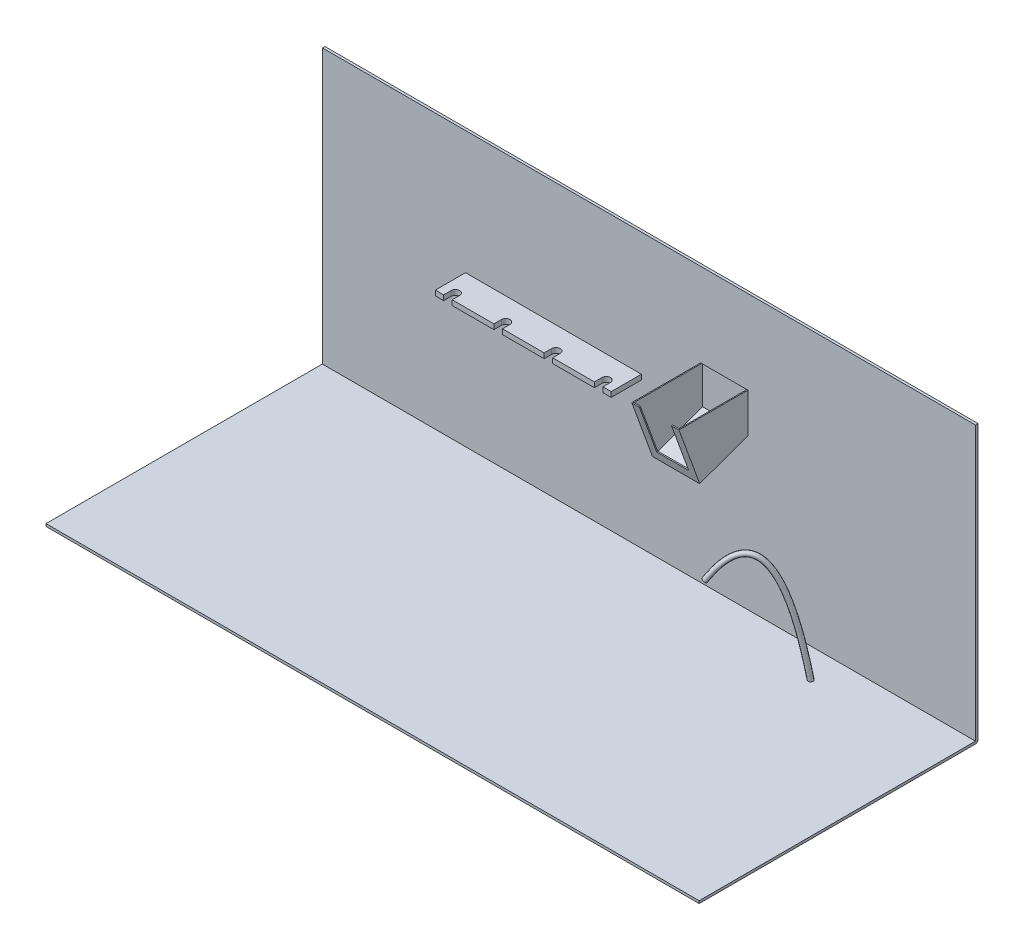
SolidWorks part; units mm, degrees
ref_plane "Front Plane" through (0, 0, 0) normal (0, 0, 1) x (1, 0, 0)
ref_plane "Top Plane" through (0, 0, 0) normal (0, 1, 0) x (1, 0, 0)
ref_plane "Right Plane" through (0, 0, 0) normal (1, 0, 0) x (0, 0, -1)
sketch "Sketch1" plane through (0, 0, 0) normal (0, 0, 1) x (1, 0, 0)
  line L1 (-650, -2.5) -> (650, -2.5)
  line L2 (-650, -2.5) -> (-650, 2.5)
  line L3 (-650, 2.5) -> (650, 2.5)
  line L4 (650, -2.5) -> (650, 2.5)
  line L5 (-650, -2.5) -> (650, 2.5) construction
  line L6 (-650, 2.5) -> (650, -2.5) construction
  point P0 (0, 0)
  dimension "D1" = 5
  dimension "D2" = 1300
extrude "Boss-Extrude1" add sketch "Sketch1" along normal mid plane 550
sketch "Sketch2" plane through (0, 0, -275) normal (0, 0, -1) x (-1, 0, 0)
  line L0 (-650, -2.5) -> (-650, 547.5)
  line L1 (-650, 547.5) -> (650, 547.5)
  line L2 (650, 547.5) -> (650, -2.5)
  line L3 (650, -2.5) -> (-650, -2.5)
  line L4 (650, 2.5) -> (650, -2.5) construction
  dimension "D1" = 550
extrude "Boss-Extrude2" add sketch "Sketch2" along normal blind 5
fillet "Fillet1" radius 5 1 edges at (0, -2.5, -280)
sketch "Sketch3" plane through (0, 0, -275) normal (0, 0, 1) x (1, 0, 0)
  line L0 (-650, 2.5) -> (-650, 547.5) construction
  line L1 (-365, 302.5) -> (-15, 302.5)
  line L2 (-365, 302.5) -> (-365, 292.5)
  line L3 (-365, 292.5) -> (-15, 292.5)
  line L4 (-15, 302.5) -> (-15, 292.5)
  line L5 (-365, 302.5) -> (-15, 292.5) construction
  line L6 (-365, 292.5) -> (-15, 302.5) construction
  line L8 (650, 2.5) -> (-650, 2.5) construction
  point P0 (-190, 297.5)
  dimension "D1" = 350
  dimension "D2" = 460
  dimension "D3" = 10
  dimension "D4" = 300
extrude "Boss-Extrude3" add sketch "Sketch3" along normal blind 60
sketch "Sketch4" plane through (0, 302.5, 0) normal (0, 1, 0) x (1, 0, 0)
  line L0 (-348.5, 230) -> (-348.5, 215)
  line L1 (-15, 215) -> (-365, 215) construction
  line L2 (-331.5, 230) -> (-331.5, 215)
  line L3 (-331.5, 215) -> (-348.5, 215)
  line L4 (-365, 215) -> (-365, 275) construction
  arc A0 (-331.5, 230) -> (-348.5, 230) centre (-340, 230) ccw
  dimension "D1" = 17
  dimension "D3" = 25
  dimension "D2" = 15
extrude "Cut-Extrude1" cut sketch "Sketch4" against normal up to next
pattern_linear "LPattern1" count 4 spacing 100 along (1, 0, 0) of "Cut-Extrude1"
sketch "Sketch5" [suppressed] plane through (0, 0, -275) normal (0, 0, 1) x (1, 0, 0)
  line L0 (160, 597.5) -> (160, 186.1013) construction
  line L1 (-650, 597.5) -> (650, 597.5) construction
  line L2 (650, 597.5) -> (650, 2.5) construction
  line L3 (115, 357.5) -> (205, 357.5)
  line L4 (205, 357.5) -> (205, 467.5)
  line L5 (205, 467.5) -> (210, 467.5)
  line L6 (210, 467.5) -> (210, 352.5)
  line L7 (210, 352.5) -> (110, 352.5)
  line L8 (110, 352.5) -> (110, 467.5)
  line L9 (110, 467.5) -> (115, 467.5)
  line L10 (115, 467.5) -> (115, 357.5)
  line L11 (650, 2.5) -> (-650, 2.5) construction
  dimension "D1" = 490
  dimension "D2" = 90
  dimension "D3" = 5
  dimension "D4" = 5
  dimension "D5" = 5
  dimension "D6" = 110
  dimension "D7" = 350
extrude "Boss-Extrude4" [suppressed] add sketch "Sketch5" along normal blind 100
sketch "Sketch6" [suppressed] plane through (0, 357.5, 0) normal (0, 1, 0) x (1, 0, 0)
  line L0 (115, 231.5) -> (205, 231.5)
  line L1 (115, 175) -> (115, 275) construction
  line L2 (205, 175) -> (205, 275) construction
  line L3 (115, 231.5) -> (115, 235.5)
  line L4 (205, 218.5) -> (115, 218.5)
  line L5 (115, 175) -> (115, 275) construction
  line L6 (115, 218.5) -> (115, 214.5)
  line L7 (115, 214.5) -> (205, 214.5)
  line L8 (205, 214.5) -> (205, 218.5)
  line L9 (115, 235.5) -> (205, 235.5)
  line L10 (205, 235.5) -> (205, 231.5)
  line L11 (115, 225) -> (205, 225) construction
  dimension "D1" = 4
  dimension "D2" = 4
  dimension "D3" = 13
extrude "Boss-Extrude5" [suppressed] add sketch "Sketch6" along normal blind 11
sketch "Sketch7" [suppressed] plane through (0, 0, -175) normal (0, 0, 1) x (1, 0, 0)
  line L0 (110, 467.5) -> (110, 352.5)
  line L1 (110, 352.5) -> (210, 352.5)
  line L2 (210, 352.5) -> (210, 467.5)
  line L3 (210, 467.5) -> (195, 467.5)
  line L4 (195, 467.5) -> (195, 357.5)
  line L5 (115, 357.5) -> (205, 357.5) construction
  line L6 (195, 357.5) -> (125, 357.5)
  line L7 (205, 357.5) -> (115, 357.5) construction
  line L8 (125, 357.5) -> (125, 467.5)
  line L9 (125, 467.5) -> (110, 467.5)
  dimension "D1" = 15
extrude "Boss-Extrude6" [suppressed] add sketch "Sketch7" along normal blind 2
ref_plane "Plane1" through (150, 0, 0) normal (1, 0, 0) x (0, 0, -1)
sketch "Sketch9" plane through (150, 0, 0) normal (1, 0, 0) x (0, 0, -1)
  line L0 (181.0307, 268.298) -> (275, 302.5)
  line L1 (275, 547.5) -> (275, 2.5) construction
  line L2 (275, 302.5) -> (275, 381.0611)
  line L3 (275, 381.0611) -> (139.9883, 381.0611)
  line L4 (139.9883, 381.0611) -> (181.0307, 268.298)
  line L5 (-275, 2.5) -> (275, 2.5) construction
  dimension "D1" = 300
  dimension "D2" = 100
  dimension "D3" = 110
  dimension "D4" = 120
extrude "Boss-Extrude7" add sketch "Sketch9" along normal mid plane 94
shell "Shell1" thickness 2 removed face at (150, 381.0611, -207.4942) removed face at (150, 324.6795, -160.5095)
sketch "Sketch10" plane through (0, 89.5671, -246.0835) normal (0, -0.342, 0.9397) x (1, 0, 0)
  line L0 (103, 310.2015) -> (103, 190.2015)
  line L1 (103, 190.2015) -> (197, 190.2015)
  line L2 (197, 190.2015) -> (197, 310.2015)
  line L3 (197, 310.2015) -> (182, 310.2015)
  line L4 (182, 310.2015) -> (182, 210.2015)
  line L5 (182, 210.2015) -> (118, 210.2015)
  line L6 (118, 210.2015) -> (118, 310.2015)
  line L7 (118, 310.2015) -> (103, 310.2015)
  dimension "D1" = 15
  dimension "D2" = 20
extrude "Boss-Extrude8" add sketch "Sketch10" along normal blind 2
sketch "Sketch12" plane through (0, 180.6103, 65.7368) normal (0, 0.9397, 0.342) x (1, 0, 0)
  line L0 (105, 313.3047) -> (195, 313.3047) construction
  line L1 (105, 261.8766) -> (105, 364.7329) construction
  line L2 (195, 261.8766) -> (195, 364.7329) construction
  line L6 (170, 333.3047) -> (130, 333.3047)
  line L9 (170, 293.3047) -> (130, 293.3047)
  line L12 (130, 333.3047) -> (130, 293.3047)
  line L14 (135, 328.3047) -> (135, 298.3047)
  line L15 (150, 313.3047) -> (150, 352.8874) construction
  line L16 (165, 328.3047) -> (165, 298.3047)
  line L17 (170, 333.3047) -> (170, 293.3047)
  line L18 (135, 328.3047) -> (165, 328.3047)
  line L19 (135, 298.3047) -> (165, 298.3047)
  dimension "D1" = 30
  dimension "D2" = 40
  dimension "D3" = 5
  dimension "D4" = 5
  dimension "D5" = 30
extrude "Boss-Extrude9" add sketch "Sketch12" along normal blind 10
sketch "Sketch13" plane through (0, 0, -275) normal (0, 0, 1) x (1, 0, 0)
  line L0 (650, 2.5) -> (-650, 2.5) construction
  line L1 (450, 2.5) -> (450, 206.5407) construction
  point P0 (450, 2.5)
  dimension "D1" = 1100
ref_plane "Plane2" through (50.5181, 0, 60.2051) normal (0.6428, 0, 0.766) x (0, 1, 0)
sketch "Sketch14" plane through (50.5181, 0, 60.2051) normal (0.6428, 0, 0.766) x (0, 1, 0)
  line L0 (2.5, -674.6955) -> (2.5, 321.1623) construction
  spline S0 degree 2 poles (2.5, -430.563) (317.6042, -379.3338) (165.2989, -280.7866) knots 0 0 0 1 1 1
sketch "Sketch16" plane through (0, 2.5, 0) normal (0, 1, 0) x (1, 0, 0)
  circle A0 centre (380.3485, 216.5555) radius 5
  dimension "D1" = 10
sweep "Sweep1" add profiles "Sketch16" path "Sketch14"
